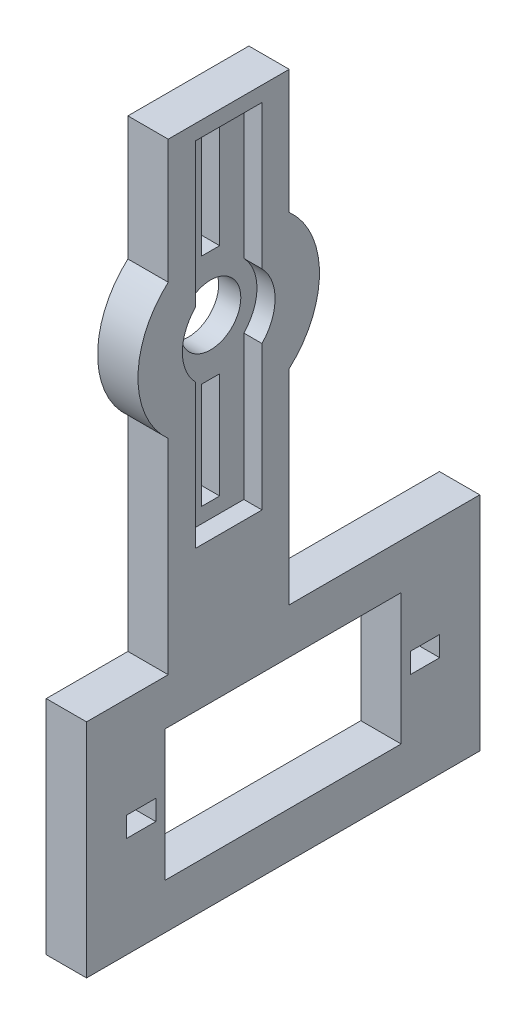
SolidWorks part; units mm, degrees
ref_plane "Front Plane" through (0, 0, 0) normal (0, 0, 1) x (1, 0, 0)
ref_plane "Top Plane" through (0, 0, 0) normal (0, 1, 0) x (1, 0, 0)
ref_plane "Right Plane" through (0, 0, 0) normal (1, 0, 0) x (0, 0, -1)
sketch "Sketch1" plane through (0, 0, 0) normal (1, 0, 0) x (0, 0, -1)
  circle A0 centre (-66, 18) radius 9
extrude "Boss-Extrude1" add sketch "Sketch1" along normal blind 4 from offset 59.6 offset against normal yes
sketch "Sketch2" plane through (0, 0, 0) normal (0, 0, 1) x (1, 0, 0)
  line L1 (-59.6, -12) -> (-55.6, -12)
  line L2 (-59.6, -12) -> (-59.6, 37)
  line L3 (-59.6, 37) -> (-55.6, 37)
  line L4 (-55.6, -12) -> (-55.6, 37)
extrude "Boss-Extrude2" add sketch "Sketch2" along normal blind 12 from offset 60
sketch "Sketch3" plane through (0, 0, 0) normal (0, 0, 1) x (1, 0, 0)
  line L1 (-59.6, -31) -> (-55.6, -31)
  line L2 (-59.6, -31) -> (-59.6, -9)
  line L3 (-59.6, -9) -> (-55.6, -9)
  line L4 (-55.6, -31) -> (-55.6, -9)
extrude "Boss-Extrude3" add sketch "Sketch3" along normal blind 39 from offset 41.1
sketch "Sketch4" plane through (0, 0, 0) normal (1, 0, 0) x (0, 0, -1)
  circle A0 centre (-66, 18) radius 4.6
extrude "Boss-Extrude4" add sketch "Sketch4" along normal blind 2.3 from offset 57.4 separate body offset against normal yes
combine bodies "Combine1" operation type subtract main body 103 bodies to subtract 104
sketch "Sketch5" plane through (0, 0, 0) normal (0, 0, 1) x (1, 0, 0)
  line L1 (-57.4, 18) -> (-55.1, 18)
  line L2 (-57.4, 18) -> (-57.4, 35.5)
  line L3 (-57.4, 35.5) -> (-55.1, 35.5)
  line L4 (-55.1, 18) -> (-55.1, 35.5)
extrude "Boss-Extrude5" add sketch "Sketch5" along normal blind 6.6 from offset 62.7 separate body
combine bodies "Combine2" operation type subtract main body 105 bodies to subtract 106
sketch "Sketch6" plane through (0, 0, 0) normal (0, 0, 1) x (1, 0, 0)
  line L1 (-60.6, 23.5) -> (-54.6, 23.5)
  line L2 (-60.6, 23.5) -> (-60.6, 34)
  line L3 (-60.6, 34) -> (-54.6, 34)
  line L4 (-54.6, 23.5) -> (-54.6, 34)
extrude "Boss-Extrude6" add sketch "Sketch6" along normal blind 1.8 from offset 65.1 separate body
combine bodies "Combine3" operation type subtract main body 107 bodies to subtract 108
sketch "Sketch7" plane through (0, 0, 0) normal (0, 0, 1) x (1, 0, 0)
  line L1 (-57.4, 0.5) -> (-55.1, 0.5)
  line L2 (-57.4, 0.5) -> (-57.4, 18)
  line L3 (-57.4, 18) -> (-55.1, 18)
  line L4 (-55.1, 0.5) -> (-55.1, 18)
extrude "Boss-Extrude7" add sketch "Sketch7" along normal blind 6.6 from offset 62.7 separate body
combine bodies "Combine4" operation type subtract main body 109 bodies to subtract 110
sketch "Sketch8" plane through (0, 0, 0) normal (0, 0, 1) x (1, 0, 0)
  line L1 (-60.6, 2) -> (-54.6, 2)
  line L2 (-60.6, 2) -> (-60.6, 12.5)
  line L3 (-60.6, 12.5) -> (-54.6, 12.5)
  line L4 (-54.6, 2) -> (-54.6, 12.5)
extrude "Boss-Extrude8" add sketch "Sketch8" along normal blind 1.8 from offset 65.1 separate body
combine bodies "Combine5" operation type subtract main body 111 bodies to subtract 112
sketch "Sketch9" plane through (0, 0, 0) normal (1, 0, 0) x (0, 0, -1)
  circle A0 centre (-66, 18) radius 3
extrude "Boss-Extrude9" add sketch "Sketch9" along normal blind 6 from offset 60.6 separate body offset against normal yes
combine bodies "Combine6" operation type subtract main body 113 bodies to subtract 114
sketch "Sketch10" plane through (0, 0, 0) normal (0, 0, 1) x (1, 0, 0)
  line L1 (-60.6, -26.5) -> (-54.6, -26.5)
  line L2 (-60.6, -26.5) -> (-60.6, -13.5)
  line L3 (-60.6, -13.5) -> (-54.6, -13.5)
  line L4 (-54.6, -26.5) -> (-54.6, -13.5)
extrude "Boss-Extrude10" add sketch "Sketch10" along normal blind 23.4 from offset 48.9 separate body
combine bodies "Combine7" operation type subtract main body 115 bodies to subtract 116
sketch "Sketch11" plane through (0, 0, 0) normal (0, 0, 1) x (1, 0, 0)
  line L1 (-60.6, -21) -> (-54.6, -21)
  line L2 (-60.6, -21) -> (-60.6, -19)
  line L3 (-60.6, -19) -> (-54.6, -19)
  line L4 (-54.6, -21) -> (-54.6, -19)
extrude "Boss-Extrude11" add sketch "Sketch11" along normal blind 2.9 from offset 45.075 separate body
combine bodies "Combine8" operation type subtract main body 117 bodies to subtract 118
sketch "Sketch12" plane through (0, 0, 0) normal (0, 0, 1) x (1, 0, 0)
  line L1 (-60.6, -21) -> (-54.6, -21)
  line L2 (-60.6, -21) -> (-60.6, -19)
  line L3 (-60.6, -19) -> (-54.6, -19)
  line L4 (-54.6, -21) -> (-54.6, -19)
extrude "Boss-Extrude12" add sketch "Sketch12" along normal blind 2.9 from offset 73.225 separate body
combine bodies "Combine9" operation type subtract main body 119 bodies to subtract 120
